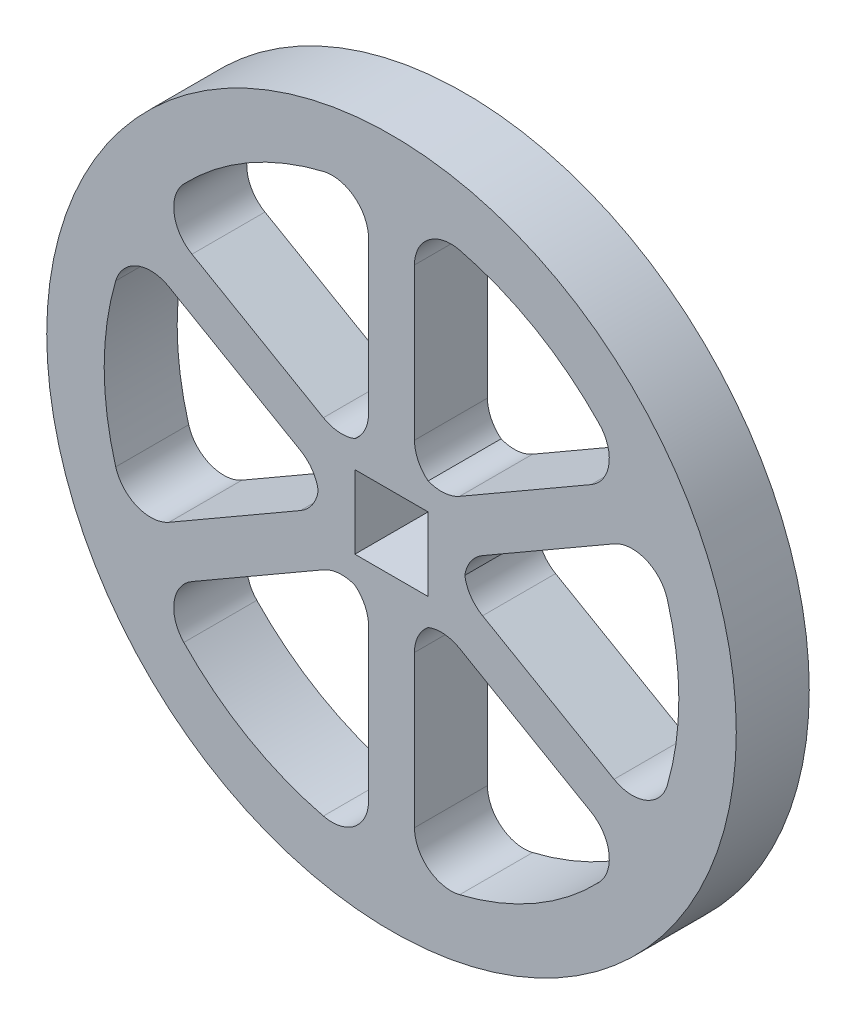
SolidWorks part; units mm, degrees
ref_plane "Front Plane" through (0, 0, 0) normal (0, 0, 1) x (1, 0, 0)
ref_plane "Top Plane" through (0, 0, 0) normal (0, 1, 0) x (1, 0, 0)
ref_plane "Right Plane" through (0, 0, 0) normal (1, 0, 0) x (0, 0, -1)
sketch "Sketch1" plane through (0, 0, 0) normal (0, 0, 1) x (1, 0, 0)
  line L0 (0, 25) -> (0, 6.35) construction
  line L1 (-2, 24.9199) -> (-2, 6.35)
  line L2 (0, 0) -> (0, 36.7755) construction
  line L3 (2, 24.9199) -> (2, 6.35)
  line L4 (-2, 6.35) -> (-2, 6.0268)
  line L5 (2, 6.35) -> (2, 6.0268)
  line L6 (20.5812, 14.192) -> (4.4993, 4.9071)
  line L7 (22.5812, 10.7279) -> (6.4993, 1.4429)
  line L8 (22.5812, -10.7279) -> (6.4993, -1.4429)
  line L9 (20.5812, -14.192) -> (4.4993, -4.9071)
  line L10 (2, -24.9199) -> (2, -6.35)
  line L11 (-2, -24.9199) -> (-2, -6.35)
  line L12 (-20.5812, -14.192) -> (-4.4993, -4.9071)
  line L13 (-22.5812, -10.7279) -> (-6.4993, -1.4429)
  line L14 (-22.5812, 10.7279) -> (-6.4993, 1.4429)
  line L15 (-20.5812, 14.192) -> (-4.4993, 4.9071)
  line L16 (2, 25) -> (2, 6.35) construction
  line L17 (-2, 25) -> (-2, 6.35) construction
  line L18 (6.4993, 1.4429) -> (6.2194, 1.2814)
  line L19 (4.4993, 4.9071) -> (4.2194, 4.7455)
  line L20 (4.4993, -4.9071) -> (4.2194, -4.7455)
  line L21 (6.4993, -1.4429) -> (6.2194, -1.2814)
  line L22 (-2, -6.35) -> (-2, -6.0268)
  line L23 (2, -6.35) -> (2, -6.0268)
  line L24 (-6.4993, -1.4429) -> (-6.2194, -1.2814)
  line L25 (-4.4993, -4.9071) -> (-4.2194, -4.7455)
  line L26 (-4.4993, 4.9071) -> (-4.2194, 4.7455)
  line L27 (-6.4993, 1.4429) -> (-6.2194, 1.2814)
  circle A0 centre (0, 0) radius 30
  circle A1 centre (0, 0) radius 6.35
  circle A2 centre (0, 0) radius 25
  point P38 (0, 0)
  point P61 (0, 0)
  dimension "D1" = 60
  dimension "D3" = 12.7
  dimension "D2" = 5
  dimension "D4" = 2
  dimension "D5" = 2
  dimension "D6" = 6
  dimension "D7" = 6
extrude "Boss-Extrude1" add sketch "Sketch1" along normal blind 6.35 contours A0 A2 | L15 A2 L14 L27 A1 L26 | L3 A2 L1 L4 A1 L5 | L7 A2 L6 L19 A1 L18 | L9 A2 L8 L21 A1 L20 | L11 A2 L10 L23 A1 L22 | L13 A2 L12 L25 A1 L24 | A1 region at (0, 15.6081, 0) region at (-13.517, 7.8041, 0) region at (13.517, 7.8041, 0) region at (-13.517, -7.8041, 0) region at (13.517, -7.8041, 0) region at (0, -15.6081, 0) region at (-29.1515, 0, 0)
fillet "Fillet1" radius 3.175 24 edges at (-22.5812, -10.7279, 3.175) (-22.5812, 10.7279, 3.175) (-20.5812, -14.192, 3.175) (-2, -24.9199, 3.175) (20.5812, -14.192, 3.175) (2, -24.9199, 3.175) (22.5812, -10.7279, 3.175) (22.5812, 10.7279, 3.175) (2, 24.9199, 3.175) (20.5812, 14.192, 3.175) (-2, 24.9199, 3.175) (-20.5812, 14.192, 3.175) (4.2194, 4.7455, 3.175) (2, 6.0268, 3.175) (6.2194, -1.2814, 3.175) (6.2194, 1.2814, 3.175) (2, -6.0268, 3.175) (4.2194, -4.7455, 3.175) (-4.2194, 4.7455, 3.175) (-2, 6.0268, 3.175) (-6.2194, -1.2814, 3.175) (-6.2194, 1.2814, 3.175) (-4.2194, -4.7455, 3.175) (-2, -6.0268, 3.175)
sketch "Sketch2" plane through (0, 0, 0) normal (0, 0, -1) x (-1, 0, 0)
  line L1 (3.1877, -3.1877) -> (-3.1877, -3.1877)
  line L2 (3.1877, -3.1877) -> (3.1877, 3.1877)
  line L3 (3.1877, 3.1877) -> (-3.1877, 3.1877)
  line L4 (-3.1877, -3.1877) -> (-3.1877, 3.1877)
  line L5 (3.1877, -3.1877) -> (-3.1877, 3.1877) construction
  line L6 (3.1877, 3.1877) -> (-3.1877, -3.1877) construction
  point P0 (0, 0)
  dimension "D1" = 6.3754
extrude "Cut-Extrude1" cut sketch "Sketch2" against normal blind 17.462
